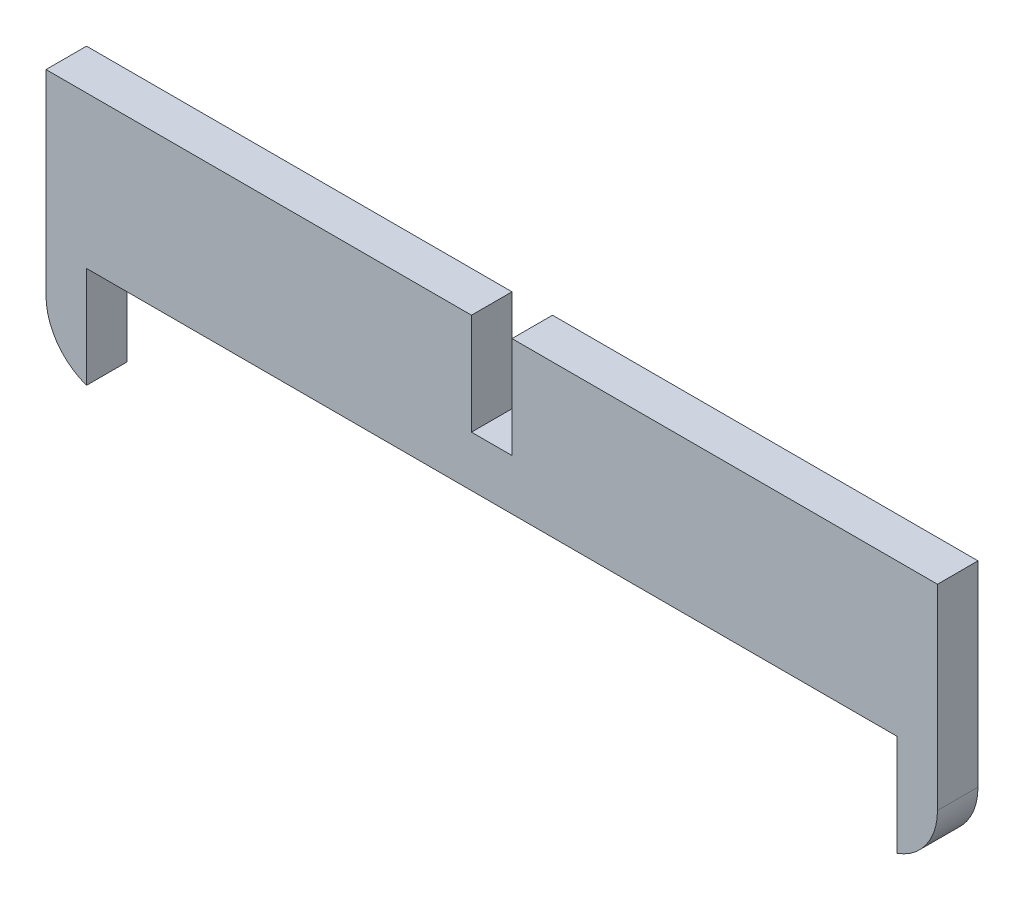
SolidWorks part; units mm, degrees
ref_plane "Front Plane" through (0, 0, 0) normal (0, 0, 1) x (1, 0, 0)
ref_plane "Top Plane" through (0, 0, 0) normal (0, 1, 0) x (1, 0, 0)
ref_plane "Right Plane" through (0, 0, 0) normal (1, 0, 0) x (0, 0, -1)
sketch "Sketch1" plane through (0, 0, 0) normal (0, 0, 1) x (1, 0, 0)
  line L1 (-55.88, -9.525) -> (55.88, -9.525)
  line L2 (-55.88, -9.525) -> (-55.88, 9.525)
  line L3 (-55.88, 9.525) -> (55.88, 9.525)
  line L4 (55.88, -9.525) -> (55.88, 9.525)
  line L5 (-55.88, -9.525) -> (55.88, 9.525) construction
  line L6 (-55.88, 9.525) -> (55.88, -9.525) construction
  point P0 (0, 0)
  dimension "D1" = 111.76
  dimension "D2" = 19.05
extrude "Boss-Extrude1" add sketch "Sketch1" along normal blind 5.08
sketch "Sketch3" plane through (0, 0, 5.08) normal (0, 0, 1) x (1, 0, 0)
  line L0 (0, 9.525) -> (0, -9.525) construction
  line L1 (55.88, 9.525) -> (-55.88, 9.525) construction
  line L3 (-2.54, -28.575) -> (2.54, -28.575)
  line L4 (-2.54, -28.575) -> (-2.54, 9.525)
  line L5 (-2.54, 9.525) -> (2.54, 9.525)
  line L6 (2.54, -28.575) -> (2.54, 9.525)
  line L7 (-2.54, -28.575) -> (2.54, 9.525) construction
  line L8 (-2.54, 9.525) -> (2.54, -28.575) construction
  dimension "D1" = 38.1
  dimension "D2" = 5.08
extrude "Cut-Extrude1" [suppressed] cut sketch "Sketch3" against normal through all
ref_axis "Axis1" through (0, 9.525, 5.08) along (0, 0, -1)
ref_plane "Plane1" through (0, 0, 0) normal (1, 0, 0) x (0, 0, -1)
sketch "Sketch5" plane through (0, -9.525, 0) normal (0, -1, 0) x (1, 0, 0)
  line L0 (-55.88, 0) -> (55.88, 0) construction
  line L1 (-55.88, 5.08) -> (-50.8, 5.08)
  line L2 (-55.88, 5.08) -> (-55.88, 0)
  line L3 (-55.88, 0) -> (-50.8, 0)
  line L4 (-50.8, 5.08) -> (-50.8, 0)
  dimension "D1" = 5.08
extrude "Boss-Extrude3" add sketch "Sketch5" along normal blind 12.7
mirror "Mirror1" about plane through (0, 0, 0) normal (1, 0, 0) of "Boss-Extrude3"
fillet "Fillet2" radius 7.62 2 edges at (-55.88, -22.225, 2.54) (55.88, -22.225, 2.54)
sketch "Sketch7" plane through (0, 0, 5.08) normal (0, 0, 1) x (1, 0, 0)
  line L0 (0, 9.525) -> (0, 3.175) construction
  line L1 (55.88, 9.525) -> (-55.88, 9.525) construction
  line L3 (-2.54, -3.175) -> (2.54, -3.175)
  line L4 (-2.54, -3.175) -> (-2.54, 9.525)
  line L5 (-2.54, 9.525) -> (2.54, 9.525)
  line L6 (2.54, -3.175) -> (2.54, 9.525)
  line L7 (-2.54, -3.175) -> (2.54, 9.525) construction
  line L8 (-2.54, 9.525) -> (2.54, -3.175) construction
  dimension "D2" = 5.08
  dimension "D1" = 6.35
extrude "Cut-Extrude2" cut sketch "Sketch7" against normal through all
equation "\"Foamcore\" = .1in"
equation "\"MDF\" = .2in"
equation "\"Gmaterial\"= \"MDF\""
equation "\"PVC-ID\" = \"1.590in\""
equation "\"PVC-OD\" = \"1.900in\""
equation "\"D1@Sketch1\"=\"Gmaterial\"*2+4"
equation "\"D1@Boss-Extrude1\"=\"Gmaterial\""
equation "\"D2@Sketch3\"=\"Gmaterial\""
equation "\"D2@Sketch7\"=\"Gmaterial\""
